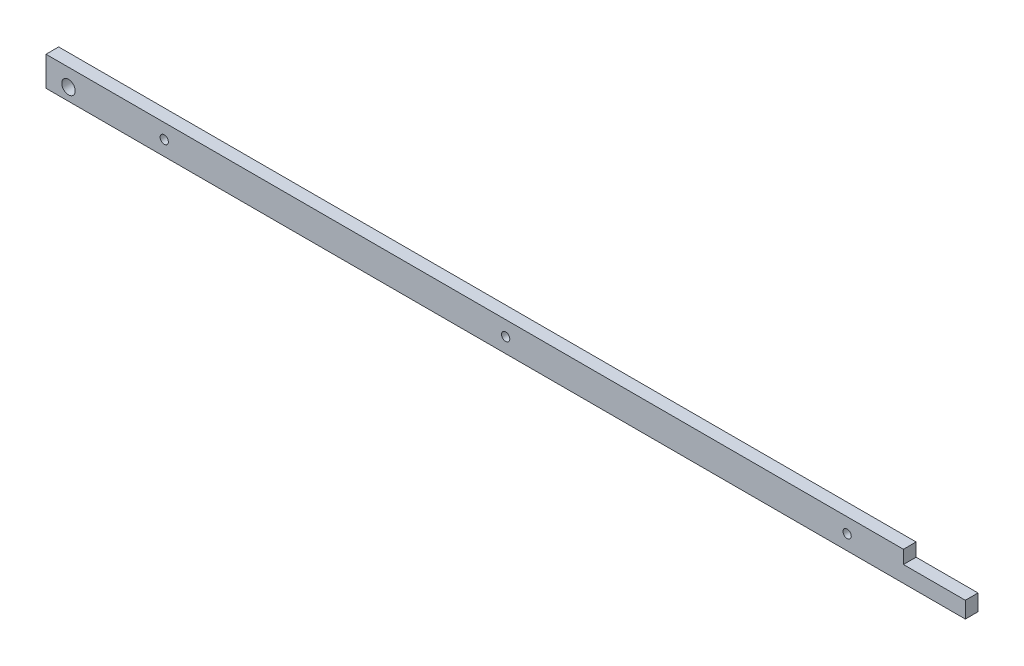
SolidWorks part; units mm, degrees
ref_plane "Front Plane" through (0, 0, 0) normal (0, 0, 1) x (1, 0, 0)
ref_plane "Top Plane" through (0, 0, 0) normal (0, 1, 0) x (1, 0, 0)
ref_plane "Right Plane" through (0, 0, 0) normal (1, 0, 0) x (0, 0, -1)
sketch "Sketch1" plane through (0, 0, 0) normal (0, 0, 1) x (1, 0, 0)
  line L0 (0, 12.9644) -> (515.86, 12.9644)
  line L1 (515.86, 12.9644) -> (515.86, 5.0194)
  line L2 (515.86, 5.0194) -> (553.1, 5.0194)
  line L3 (553.1, 5.0194) -> (553.1, -4.8006)
  line L5 (0, -4.8006) -> (0, 12.9644)
  line L7 (0, -4.8006) -> (553.1, -4.8006)
  line L9 (0, 16.1394) -> (457.2, 16.1394) construction
  line L10 (0, -4.8006) -> (553.1, -4.8006) construction
  line L11 (0, -9.2606) -> (0, 41.5394) construction
  line L12 (0, 16.1394) -> (553.1, 16.1394) construction
  line L13 (-199942.0379, 4.0819) -> (200173.9064, 4.0819) construction
  line L15 (515.86, 5.0194) -> (553.1, 5.0194) construction
  line L16 (515.86, 37.0794) -> (515.86, -4.8006) construction
  circle A3 centre (481.98, 4.0819) radius 2.4892
  circle A4 centre (276.55, 4.0819) radius 2.4892
  circle A5 centre (71.12, 4.0819) radius 2.4892
  circle A6 centre (13.54, 2.5994) radius 4.0635
  circle A7 centre (71.12, 4.0819) radius 2.4892 construction
  circle A8 centre (276.55, 4.0819) radius 2.4892 construction
  circle A9 centre (481.98, 4.0819) radius 2.4892 construction
  point P9 (553.1, -4.8006)
  point P10 (515.86, 12.9644)
  point P21 (13.54, 29.6794)
  point P26 (13.54, 2.5994)
  point P33 (0, 0)
  point P37 (78.6561, 4.0819)
  point P41 (0, 0)
  point P47 (515.86, 5.0194)
  dimension "D1" = 8.127
extrude "Boss-Extrude1" add sketch "Sketch1" along normal blind 7.62
